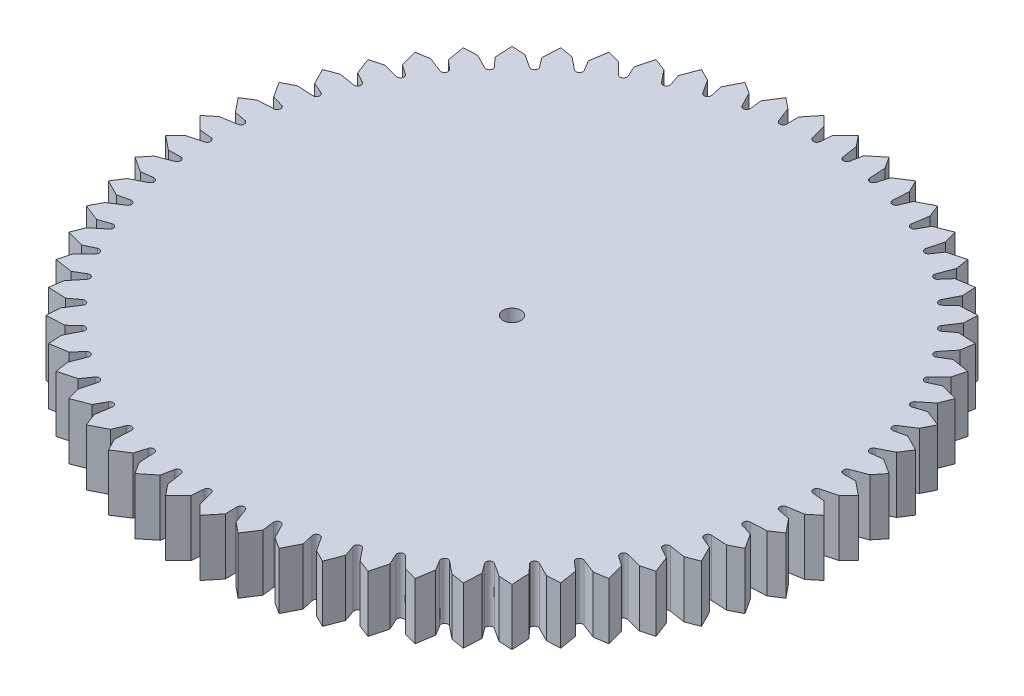
SolidWorks part; units mm, degrees
ref_plane "Front Plane" through (0, 0, 0) normal (0, 0, 1) x (1, 0, 0)
ref_plane "Top Plane" through (0, 0, 0) normal (0, 1, 0) x (1, 0, 0)
ref_plane "Right Plane" through (0, 0, 0) normal (1, 0, 0) x (0, 0, -1)
sketch "Sketch1" plane through (0, 0, 0) normal (0, 1, 0) x (1, 0, 0)
  line L0 (0, 0) -> (33.1203, 0)
  line L1 (33.1203, 0) -> (34.952, 1.8318)
  line L2 (0, 0) -> (32.9388, 3.462)
  line L3 (34.952, 1.8318) -> (32.9388, 3.462)
  dimension "D1" = 84
  dimension "D2" = 6
  dimension "D3" = 35
extrude "Boss-Extrude1" add sketch "Sketch1" along normal blind 6
ref_axis "Axis1" through (0, 6, 0) along (0, -1, 0)
pattern_circular "CirPattern1" count 60 over 360 about axis through (0, 6, 0) along (0, -1, 0) of "Boss-Extrude1"
sketch "Sketch2" plane through (0, 6, 0) normal (0, 1, 0) x (1, 0, 0)
  line L0 (33.6047, -0.4844) -> (32.3376, -0.3736)
  line L1 (34.952, -1.8318) -> (33.1203, 0) construction
  line L2 (32.2732, 0.3622) -> (33.9251, 0.8048)
  line L3 (33.1203, 0) -> (34.952, 1.8318) construction
  line L4 (33.1203, 0) -> (32.3703, 0) construction
  line L5 (33.6047, -0.4844) -> (33.1203, 0)
  line L6 (33.1203, 0) -> (33.9251, 0.8048)
  arc A0 (32.3376, -0.3736) -> (32.2732, 0.3622) centre (32.3703, 0) cw
  dimension "D1" = 0.375
  dimension "D2" = 5
  dimension "D3" = 0.75
  dimension "D4" = 15
extrude "Cut-Extrude1" cut sketch "Sketch2" against normal through all
pattern_circular "CirPattern2" count 60 over 360 about axis through (0, 6, 0) along (0, -1, 0) of "Cut-Extrude1"
sketch "Sketch3" plane through (0, 6, 0) normal (0, 1, 0) x (1, 0, 0)
  circle A0 centre (0, 0) radius 0.95
  dimension "D1" = 1.9
extrude "Cut-Extrude2" cut sketch "Sketch3" against normal through all
